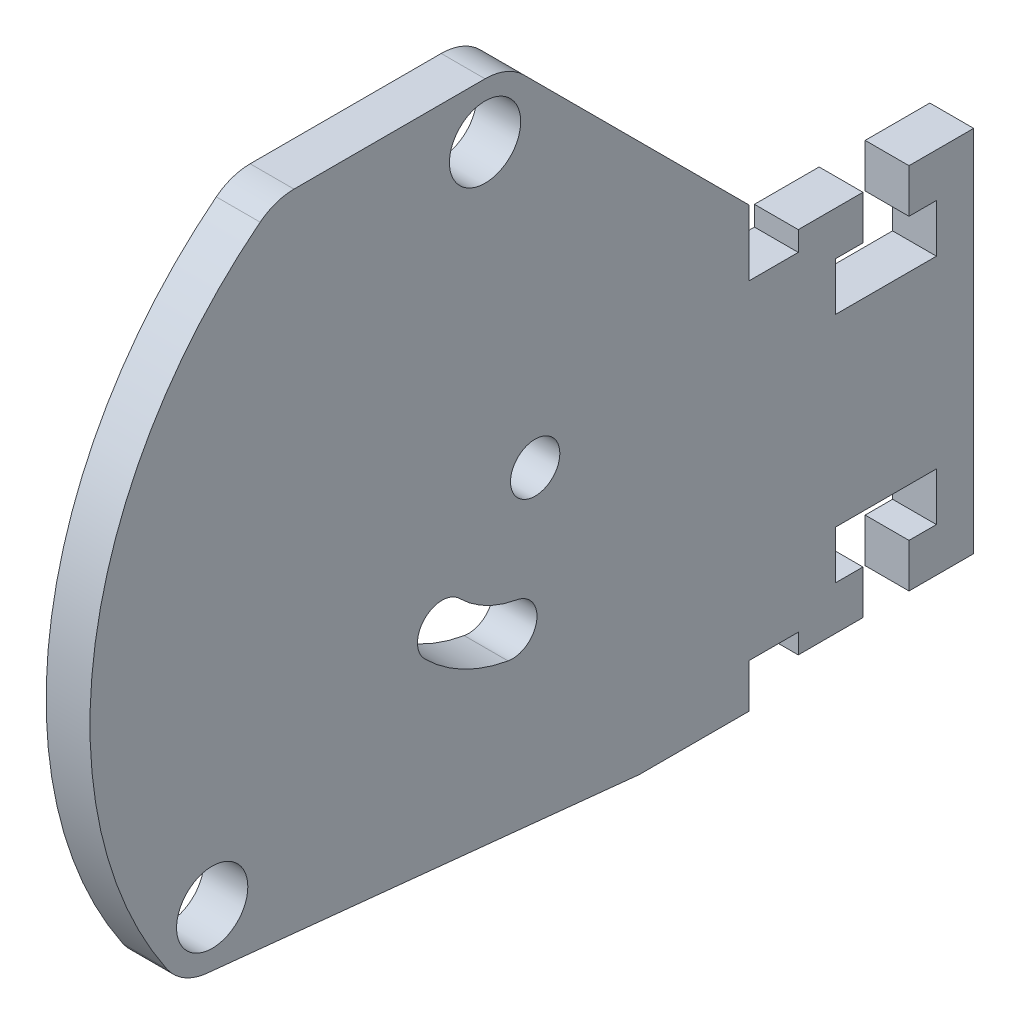
SolidWorks part; units mm, degrees
ref_plane "Front Plane" through (0, 0, 0) normal (0, 0, 1) x (1, 0, 0)
ref_plane "Top Plane" through (0, 0, 0) normal (0, 1, 0) x (1, 0, 0)
ref_plane "Right Plane" through (0, 0, 0) normal (1, 0, 0) x (0, 0, -1)
sketch "Sketch1" plane through (0, 0, 0) normal (1, 0, 0) x (0, 0, -1)
  line L0 (-16, 7.5) -> (20, 7.5) construction
  line L1 (-16, 15) -> (20, 15)
  line L2 (-16, 15) -> (-16, 0)
  line L3 (-16, 0) -> (20, 0)
  line L4 (20, 15) -> (20, 0)
  line L5 (0, 15) -> (0, 0) construction
  line L10 (0, 12.5) -> (-4.2426, 8.2574) construction
  line L11 (9.75, 15) -> (9.75, 18)
  line L12 (9.75, 18) -> (-4.5399, 32.2899)
  line L13 (20, 15) -> (12, 15)
  line L14 (20, 15) -> (20, 15.9)
  line L15 (20, 15.9) -> (12, 15.9)
  line L16 (12, 15) -> (12, 15.9)
  line L18 (16, 15.9) -> (16, -0.9) construction
  line L19 (20, 0) -> (12, 0)
  line L20 (20, 0) -> (20, -0.9)
  line L21 (20, -0.9) -> (12, -0.9)
  line L22 (12, 0) -> (12, -0.9)
  line L23 (14.95, 1.1) -> (17.05, 1.1)
  line L24 (14.95, 13.9) -> (17.05, 13.9)
  line L25 (14.95, 13.9) -> (14.95, 15.9)
  line L26 (14.95, 15.9) -> (17.05, 15.9)
  line L27 (17.05, 13.9) -> (17.05, 15.9)
  line L28 (14.95, 13.9) -> (17.05, 15.9) construction
  line L29 (14.95, 15.9) -> (17.05, 13.9) construction
  line L30 (13.7, 11.7) -> (18.3, 11.7)
  line L31 (13.7, 11.7) -> (13.7, 13.9)
  line L32 (13.7, 13.9) -> (18.3, 13.9)
  line L33 (18.3, 11.7) -> (18.3, 13.9)
  line L34 (13.7, 11.7) -> (18.3, 13.9) construction
  line L35 (13.7, 13.9) -> (18.3, 11.7) construction
  line L36 (14.95, 1.1) -> (14.95, -0.9)
  line L37 (14.95, -0.9) -> (17.05, -0.9)
  line L38 (17.05, 1.1) -> (17.05, -0.9)
  line L39 (13.7, 3.3) -> (13.7, 1.1)
  line L40 (13.7, 1.1) -> (18.3, 1.1)
  line L41 (18.3, 3.3) -> (18.3, 1.1)
  line L42 (13.7, 3.3) -> (18.3, 3.3)
  line L43 (-1.25, 29) -> (-11.8322, 29)
  line L44 (0, 12.5) -> (-1.2372, 5.4832) construction
  line L45 (4.75, -2) -> (-14.9839, 0.0129)
  line L46 (9.75, 0) -> (4.75, 0)
  line L47 (9.75, 0) -> (9.75, -2)
  line L48 (9.75, -2) -> (4.75, -2)
  line L49 (4.75, 0) -> (4.75, -2)
  circle A2 centre (0, 12.5) radius 1.125
  circle A12 centre (-4.2426, 8.2574) radius 1.125
  circle A14 centre (0, 12.5) radius 20.3039
  circle A15 centre (0, 12.5) radius 4.875
  circle A16 centre (0, 12.5) radius 7.125
  circle A17 centre (-14.7303, 2.5) radius 2.5
  circle A18 centre (-14.7303, 2.5) radius 1.625
  circle A19 centre (-2.2855, 26.5) radius 2.5
  circle A20 centre (-2.2855, 26.5) radius 1.625
  circle A21 centre (-10.9991, 26.5) radius 2.5
  circle A22 centre (-1.0419, 6.5912) radius 1.125
  point P15 (16, 14.9)
  point P34 (16, 12.8)
  dimension "D1" = 2.25
  dimension "D2" = 5
  dimension "D7" = 6
  dimension "D11" = 2.1
  dimension "D16" = 5
  dimension "D17" = 3.25
  dimension "D3" = 15
  dimension "D4" = 20
  dimension "D5" = 16
  dimension "D6" = 45
  dimension "D8" = 2.25
  dimension "D9" = 0.9
  dimension "D10" = 8
  dimension "D12" = 2
  dimension "D13" = 2.2
  dimension "D14" = 4.6
  dimension "D15" = 3
  dimension "D18" = 14
  dimension "D19" = 10
  dimension "D20" = 0.9
  dimension "D21" = 2
  dimension "D22" = 5
extrude "Base shape" add sketch "Sketch1" along normal blind 2 contours A16 L1 L11 L12 A14 L2 | A16 L1 L2 L3 L36 L40 L39 L42 L41 A14 L4 L27 L32 L33 L30 L31 L25 | L1 A16 A15 | L1 A16 A12 A15 | L1 A15 A2 | L1 A15 | A16 L1 A15 | A14 L38 L3 L4 L41 L40 | L3 L38 L21 L20 | L36 L3 L22 L21 | L1 L25 L15 L16 | A18 L2 A17 | A18 L2 A17 | A19 A20 | A21 | A14 L14 L15 | L3 L49 L48 L47 | L49 L3 L45 region at (0, 14.61, -10.875) region at (0, 19.0585, 8.5011) region at (0, 15.45, -13.475) region at (0, 9.6923, -4.2211) region at (0, 15.1412, -5.4286) region at (0, 13.7642, -4.5815) region at (0, 15.9731, 0) region at (0, 11.886, 5.7256) region at (0, 27.4296, 0.0412) region at (0, 15.45, -18.525) region at (0, 4.6164, 13.5212) region at (0, 2.5, 16.5586) region at (0, 26.5, 10.9991) region at (0, 2.8412, -19.0769) region at (0, -0.45, -18.525) region at (0, -0.6667, 1.7858) region at (0, -1, -7.25) region at (0, -0.45, -13.475)
fillet "Fillet1" [suppressed] radius 100
